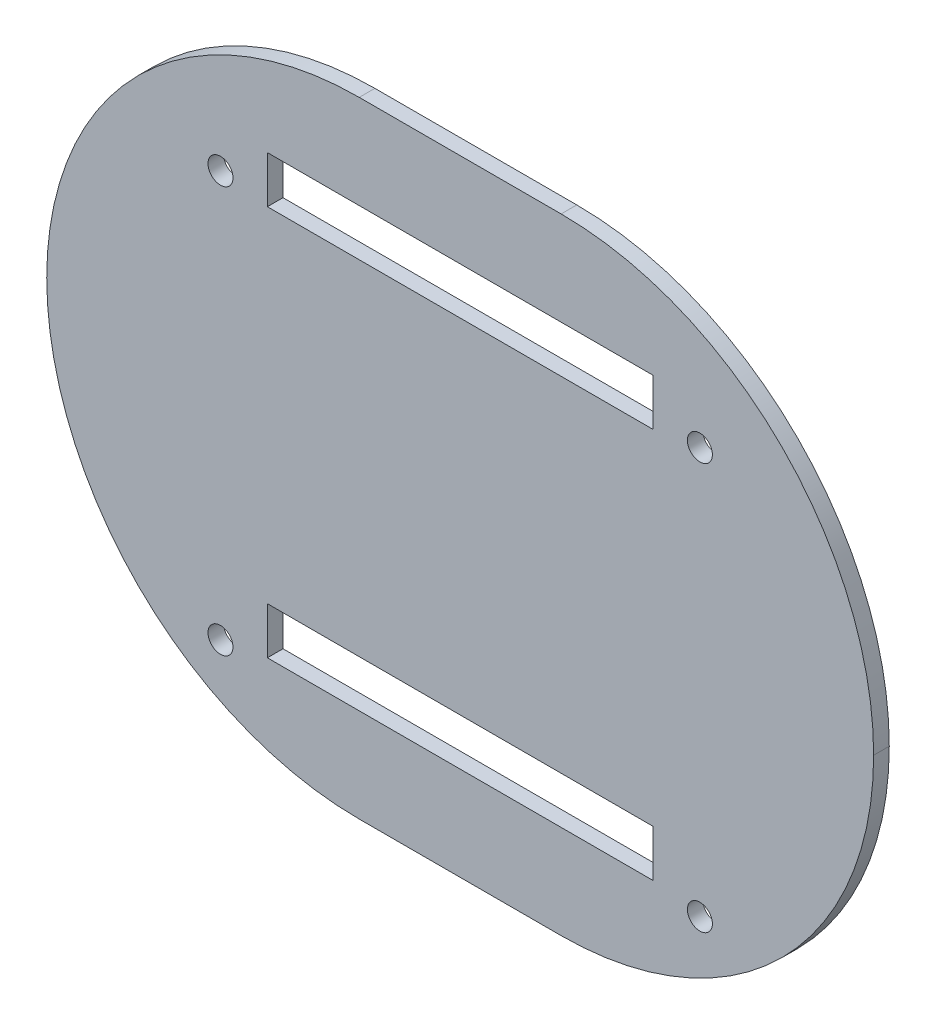
SolidWorks part; units mm, degrees
ref_plane "Front Plane" through (0, 0, 0) normal (0, 0, 1) x (1, 0, 0)
ref_plane "Top Plane" through (0, 0, 0) normal (0, 1, 0) x (1, 0, 0)
ref_plane "Right Plane" through (0, 0, 0) normal (1, 0, 0) x (0, 0, -1)
sketch "Esquisse1" plane through (0, 0, 0) normal (0, 0, 1) x (1, 0, 0)
  line L1 (0, 0) -> (-295, 0)
  line L2 (0, 0) -> (0, -260)
  line L3 (0, -260) -> (-295, -260)
  line L4 (-295, 0) -> (-295, -260)
  line L5 (-147.5, -260) -> (-147.5, 0) construction
  line L6 (0, -130) -> (-295, -130) construction
  point P152 (-147.5, -130)
  dimension "D1" = 260
  dimension "D2" = 295
extrude "Boss.-Extru.1" add sketch "Esquisse1" along normal blind 5
sketch "Esquisse3" plane through (0, 0, 0) normal (0, 0, -1) x (-1, 0, 0)
  line L1 (15.2, -30) -> (279.8, -30)
  line L2 (15.2, -30) -> (15.2, -230)
  line L3 (15.2, -230) -> (279.8, -230)
  line L4 (279.8, -30) -> (279.8, -230)
  line L5 (15.2, -30) -> (279.8, -230) construction
  line L6 (15.2, -230) -> (279.8, -30) construction
  line L7 (0, -260) -> (0, 0) construction
  line L8 (0, 0) -> (295, 0) construction
  line L9 (295, 0) -> (295, -260) construction
  line L10 (262.7157, -260) -> (221.6421, -260) construction
  point P0 (147.5, -130)
  dimension "D1" = 15.2
  dimension "D2" = 30
  dimension "D3" = 15.2
  dimension "D4" = 30
extrude "Enlèv. mat.-Extru.2" cut sketch "Esquisse3" against normal through all flip side to cut
fillet "Congé1" radius 100 4 edges at (-279.8, -30, 2.5) (-15.2, -30, 2.5) (-279.8, -230, 2.5) (-15.2, -230, 2.5)
sketch "Esquisse5" plane through (0, 0, 5) normal (0, 0, 1) x (1, 0, 0)
  line L1 (-70.7995, -202.5306) -> (-224.2005, -202.5306)
  line L2 (-70.7995, -202.5306) -> (-70.7995, -72.5306)
  line L3 (-70.7995, -72.5306) -> (-224.2005, -72.5306)
  line L4 (-224.2005, -202.5306) -> (-224.2005, -72.5306)
  line L5 (-147.5, -72.5306) -> (-147.5, -202.5306) construction
  line L6 (-70.7995, -137.5306) -> (-224.2005, -137.5306) construction
  circle A0 centre (-70.7995, -202.5306) radius 4
  circle A1 centre (-224.2005, -202.5306) radius 4
  circle A2 centre (-70.7995, -72.5306) radius 4
  circle A3 centre (-224.2005, -72.5306) radius 4
  point P632 (-147.5, -137.5306)
  dimension "D3" = 8
  dimension "D1" = 20
  dimension "D2" = 20
extrude "Enlèv. mat.-Extru.4" cut sketch "Esquisse5" against normal through all contours L1 A0 L2 | L2 A0 L1 | A1 L1 L4 | A1 L4 L1 | L3 A3 L4 | L4 A3 L3 | A2 L2 L3 | A2 L3 L2 region at (-224.7664, -203.0965, 5) region at (-222.5029, -200.833, 5) region at (-72.4971, -200.833, 5) region at (-70.2336, -203.0965, 5) region at (-224.7664, -71.9647, 5) region at (-222.5029, -74.2283, 5) region at (-72.4971, -74.2283, 5) region at (-70.2336, -71.9647, 5)
sketch "Esquisse7" plane through (0, 0, 0) normal (0, 0, -1) x (-1, 0, 0)
  line L0 (279.8, -130) -> (15.2, -130) construction
  line L1 (179.8, -30) -> (115.2, -30) construction
  line L2 (209.2005, -75) -> (85.7995, -75)
  line L3 (209.2005, -75) -> (209.2005, -60)
  line L4 (209.2005, -60) -> (85.7995, -60)
  line L5 (85.7995, -75) -> (85.7995, -60)
  line L6 (147.5, -60) -> (147.5, -75) construction
  line L7 (209.2005, -67.5) -> (85.7995, -67.5) construction
  line L8 (209.2005, -192.5) -> (85.7995, -192.5) construction
  line L9 (147.5, -200) -> (147.5, -185) construction
  line L10 (85.7995, -185) -> (85.7995, -200)
  line L11 (209.2005, -200) -> (85.7995, -200)
  line L12 (209.2005, -185) -> (209.2005, -200)
  line L13 (209.2005, -185) -> (85.7995, -185)
  point P20 (147.5, -192.5)
  point P48 (147.5, -67.5)
  dimension "D1" = 15
  dimension "D2" = 15
  dimension "D3" = 30
  dimension "D4" = 15
extrude "Enlèv. mat.-Extru.6" cut sketch "Esquisse7" against normal through all
